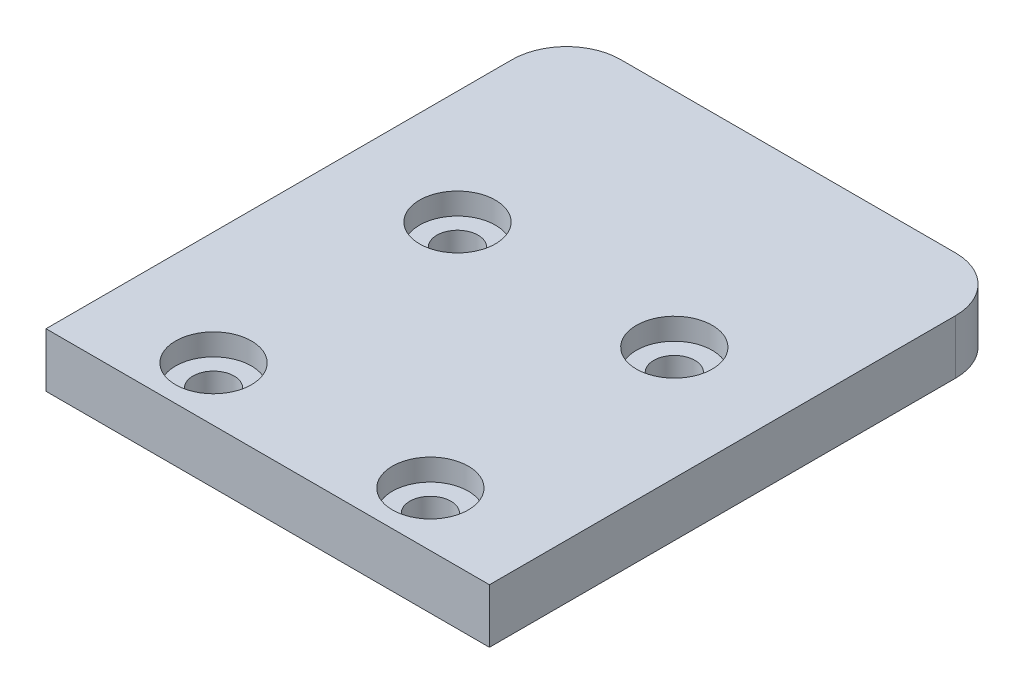
SolidWorks part; units mm, degrees
ref_plane "Plan de face" through (0, 0, 0) normal (0, 0, 1) x (1, 0, 0)
ref_plane "Plan de dessus" through (0, 0, 0) normal (0, 1, 0) x (1, 0, 0)
ref_plane "Plan de droite" through (0, 0, 0) normal (1, 0, 0) x (0, 0, -1)
sketch "Esquisse1" plane through (0, 0, 0) normal (0, 0, 1) x (1, 0, 0)
  line L0 (-8, 25) -> (0, 25)
  line L1 (-8, 25) -> (-8, 0)
  line L2 (0, 25) -> (0, 0)
  line L3 (-8, 0) -> (0, 0)
  line L4 (40.9, 25) -> (48.9, 25)
  line L5 (40.9, 25) -> (40.9, 0)
  line L6 (48.9, 25) -> (48.9, 0)
  line L7 (40.9, 0) -> (48.9, 0)
  line L8 (0, 0) -> (0, 5)
  line L9 (0, 0) -> (40.9, 0)
  line L10 (0, 5) -> (40.9, 5)
  line L11 (40.9, 0) -> (40.9, 5)
  circle A0 centre (44.75, 20) radius 2
  circle A1 centre (44.75, 10) radius 2
  circle A2 centre (-3.85, 20) radius 2
  circle A3 centre (-3.85, 10) radius 2
  dimension "D7" = 4
  dimension "D1" = 40.9
  dimension "D2" = 25
  dimension "D3" = 5
  dimension "D4" = 25
  dimension "D5" = 8
  dimension "D6" = 8
  dimension "D8" = 3.85
  dimension "D9" = 5
  dimension "D10" = 3.85
  dimension "D11" = 3.85
  dimension "D12" = 3.85
  dimension "D13" = 5
  dimension "D14" = 10
  dimension "D15" = 10
extrude "Boss.-Extru.1" add sketch "Esquisse1" along normal blind 9 and the other way blind 9 contours L1 L3 L2 L0 A3 A2 | L10 L2 L9 L5 | L5 L7 L6 L4 A1 A0 region at (-4.0216, 12.1407, 0) region at (20.45, 2.5, 0) region at (44.9216, 12.1407, 0)
sketch "Esquisse2" plane through (0, 5, 0) normal (0, 1, 0) x (1, 0, 0)
  line L0 (0, 9) -> (40.9, 9)
  line L1 (0, 9) -> (0, 16)
  line L2 (40.9, 9) -> (40.9, 16)
  line L3 (0, 16) -> (40.9, 16)
  line L4 (0, -9) -> (0, -32)
  line L5 (0, -9) -> (40.9, -9)
  line L6 (0, -32) -> (40.9, -32)
  line L7 (40.9, -9) -> (40.9, -32)
  dimension "D1" = 7
  dimension "D2" = 23
extrude "Boss.-Extru.2" add sketch "Esquisse2" against normal blind 5
sketch "Esquisse5" plane through (0, 25, 0) normal (0, 1, 0) x (1, 0, 0)
  line L0 (-8, 9) -> (0, 9)
  line L1 (-8, 9) -> (-8, -9)
  line L2 (0, 9) -> (0, -9)
  line L3 (-8, -9) -> (0, -9)
  line L4 (40.9, 9) -> (48.9, 9)
  line L5 (40.9, 9) -> (40.9, -9)
  line L6 (48.9, 9) -> (48.9, -9)
  line L7 (40.9, -9) -> (48.9, -9)
  dimension "D1" = 18
  dimension "D2" = 18
extrude "Enlèv. mat.-Extru.2" cut sketch "Esquisse5" against normal through all
sketch "Esquisse6" plane through (0, 5, 0) normal (0, 1, 0) x (1, 0, 0)
  line L0 (0, -4.5) -> (40.9, -4.5) construction
  line L1 (0, 16) -> (0, -32) construction
  line L2 (40.9, 16) -> (40.9, -32) construction
  line L3 (40.9, -4.5) -> (40.9, -27) construction
  line L4 (40.9, -27) -> (0, -27) construction
  line L5 (40.9, 16) -> (0, 16) construction
  line L6 (0, -32) -> (40.9, -32) construction
  circle A0 centre (10.45, -4.5) radius 1.9
  circle A1 centre (30.45, -4.5) radius 1.9
  circle A2 centre (10.45, -27) radius 1.9
  circle A3 centre (30.45, -27) radius 1.9
  point P20 (20.45, -4.5)
  point P21 (20.45, -27)
  dimension "D1" = 3.8
  dimension "D2" = 3.8
  dimension "D3" = 3.8
  dimension "D4" = 3.8
  dimension "D5" = 20
  dimension "D6" = 20
  dimension "D7" = 10
  dimension "D8" = 10
  dimension "D9" = 20.5
  dimension "D10" = 5
extrude "Enlèv. mat.-Extru.3" cut sketch "Esquisse6" against normal blind 10
fillet "Congé1" radius 5 2 edges at (40.9, 2.5, -16) (0, 2.5, -16)
sketch "Esquisse7" plane through (0, 5, 0) normal (0, 1, 0) x (1, 0, 0)
  circle A0 centre (10.45, -4.5) radius 3.5
  circle A1 centre (30.45, -4.5) radius 3.5
  circle A2 centre (30.45, -27) radius 3.5
  circle A3 centre (10.45, -27) radius 3.5
  dimension "D1" = 7
  dimension "D2" = 7
  dimension "D3" = 7
  dimension "D4" = 7
extrude "Enlèv. mat.-Extru.4" cut sketch "Esquisse7" against normal blind 2
